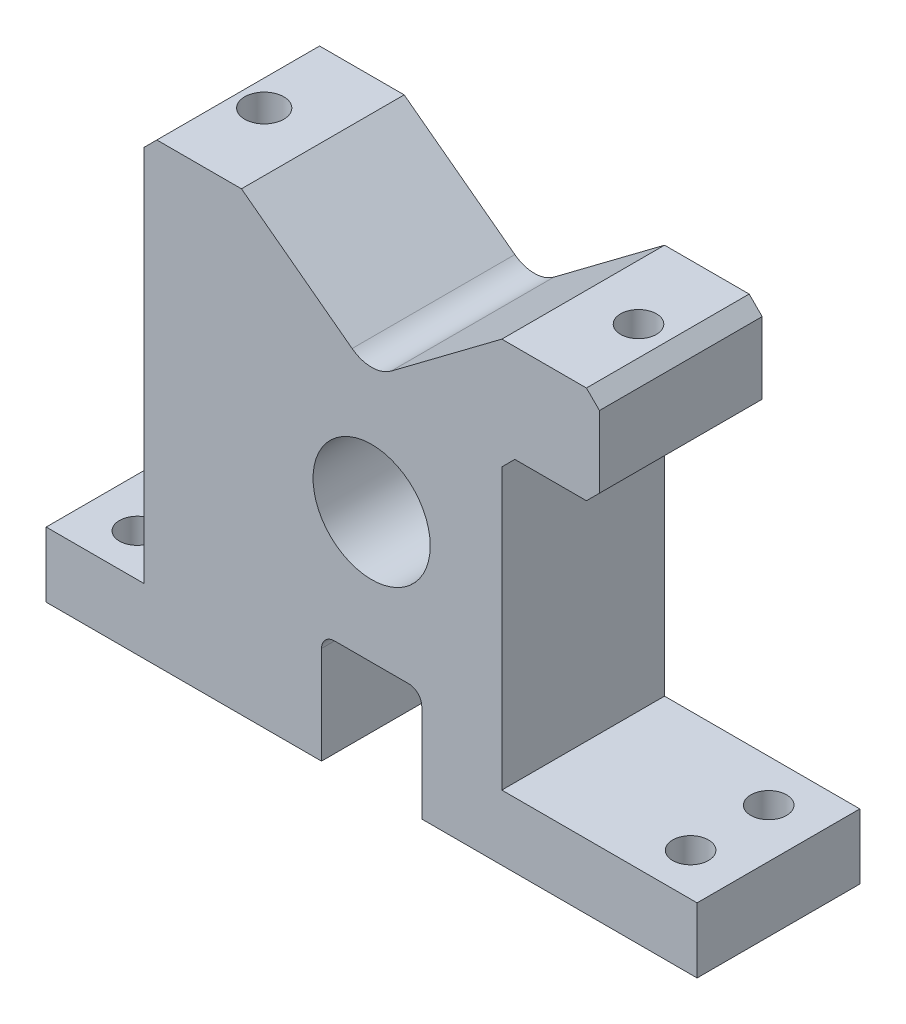
SolidWorks part; units mm, degrees
ref_plane "Front Plane" through (0, 0, 0) normal (0, 0, 1) x (1, 0, 0)
ref_plane "Top Plane" through (0, 0, 0) normal (0, 1, 0) x (1, 0, 0)
ref_plane "Right Plane" through (0, 0, 0) normal (1, 0, 0) x (0, 0, -1)
sketch "Sketch1" plane through (0, 0, 0) normal (0, 0, 1) x (1, 0, 0)
  line L1 (50, 0) -> (50, 10)
  line L2 (50, 10) -> (35, 10)
  line L4 (35, 70) -> (20, 70)
  line L5 (0, 0) -> (0, 37) construction
  line L8 (3, 57.25) -> (20, 70)
  line L9 (-3, 57.25) -> (-20, 70)
  line L10 (-35, 70) -> (-20, 70)
  line L11 (-35, 10) -> (-35, 70)
  line L12 (-50, 10) -> (-35, 10)
  line L13 (-50, 0) -> (-50, 10)
  line L14 (35, 70) -> (35, 55)
  line L16 (-5.7, 17) -> (5.7, 17)
  line L17 (7.7, 15) -> (7.7, 0)
  line L18 (7.7, 0) -> (50, 0)
  line L19 (-7.7, 0) -> (-50, 0)
  line L20 (35, 55) -> (20, 55)
  line L21 (20, 55) -> (20, 10)
  line L22 (20, 10) -> (35, 10)
  line L23 (-7.7, 15) -> (-7.7, 0)
  arc A1 (3, 57.25) -> (-3, 57.25) centre (0, 61.25) cw
  arc A2 (-7.7, 15) -> (-5.7, 17) centre (-5.7, 15) cw
  arc A3 (7.7, 15) -> (5.7, 17) centre (5.7, 15) ccw
  point P17 (0, 55)
  dimension "D1" = 5
  dimension "D2" = 2
  dimension "D3" = 15.4
extrude "Boss-Extrude1" add sketch "Sketch1" along normal blind 25
sketch "Sketch2" plane through (0, 0, 0) normal (0, 0, -1) x (-1, 0, 0)
  circle A0 centre (0, 37) radius 11.2
extrude "Cut-Extrude1" cut sketch "Sketch2" against normal through all
sketch "Sketch4" plane through (0, 10, 0) normal (0, 1, 0) x (1, 0, 0)
  line L0 (-42.5, 0) -> (-42.5, -6.5) construction
  line L3 (-35, 0) -> (-50, 0) construction
  line L4 (-42.5, -25) -> (-42.5, -18.5) construction
  line L5 (-35, -25) -> (-50, -25) construction
  line L6 (42.5, 0) -> (42.5, -6.5) construction
  line L7 (50, 0) -> (35, 0) construction
  line L8 (42.5, -25) -> (42.5, -18.5) construction
sketch "Sketch9" plane through (0, 70, 0) normal (0, 1, 0) x (1, 0, 0)
  line L0 (27.5, -25) -> (27.5, -12.5) construction
  line L1 (35, -25) -> (20, -25) construction
chamfer "Chamfer2" distance 2 angle 45 4 edges at (20, 55, 12.5) (35, 55, 12.5) (35, 70, 12.5) (-35, 70, 12.5)
sketch "Sketch11" plane through (0, 0, 25) normal (0, 0, 1) x (1, 0, 0)
  circle A0 centre (0, 37) radius 11.4
  circle A1 centre (0, 37) radius 9
extrude "Boss-Extrude3" add sketch "Sketch11" against normal blind 18
hole_wizard "M5 Clearance Hole1" positions "Sketch12" profile "Sketch13" hole size "M5" standard "ISO" end condition up to next
sketch "Sketch12" plane through (0, 10, 0) normal (0, 1, 0) x (1, 0, 0)
  point P0 (42.5, -18.5)
  point P3 (42.5, -6.5)
  point P6 (-42.5, -18.5)
  point P9 (-42.5, -6.5)
sketch "Sketch13" plane through (42.5, 10, 18.5) normal (1, 0, 0) x (0, 0, 1)
  line L0 (0, 0) -> (0, 10)
  line L1 (0, 10) -> (2.75, 10)
  line L2 (2.75, 10) -> (2.75, 0)
  line L5 (2.75, 0) -> (0, 0)
  line L11 (0, -6.35) -> (0, 107.95) construction
  dimension "Thru Hole Dia." = 5.5
  dimension "Thru Hole Depth" = 10
sketch "Sketch16" plane through (0, 70, 0) normal (0, 1, 0) x (1, 0, 0)
  line L0 (33, -12.5) -> (28.5, -12.5) construction
  line L1 (33, -25) -> (33, 0) construction
hole_wizard "M5 Clearance Hole2" positions "Sketch17" profile "Sketch18" hole size "M5" standard "ISO" end condition up to next
sketch "Sketch17" plane through (0, 70, 0) normal (0, 1, 0) x (1, 0, 0)
  point P0 (28.5, -12.5)
sketch "Sketch18" plane through (28.5, 70, 12.5) normal (1, 0, 0) x (0, 0, 1)
  line L0 (0, 0) -> (0, 15)
  line L1 (0, 15) -> (2.75, 15)
  line L2 (2.75, 15) -> (2.75, 0)
  line L5 (2.75, 0) -> (0, 0)
  line L11 (0, -6.35) -> (0, 107.95) construction
  dimension "Thru Hole Dia." = 5.5
  dimension "Thru Hole Depth" = 15
sketch "Sketch19" plane through (0, 70, 0) normal (0, 1, 0) x (1, 0, 0)
  line L0 (-33, -25) -> (-33, -12.5) construction
  line L1 (-33, 0) -> (-33, -25) construction
  line L2 (-33, -12.5) -> (-29, -12.5) construction
hole_wizard "Ø6.0mm Dowel Hole1" positions "Sketch20" profile "Sketch21" hole size "Ø6.0" standard "ISO"
sketch "Sketch20" plane through (0, 70, 0) normal (0, 1, 0) x (1, 0, 0)
  point P0 (-29, -12.5)
sketch "Sketch21" plane through (-29, 70, 12.5) normal (1, 0, 0) x (0, 0, 1)
  line L0 (0, 0) -> (0, 41.8026)
  line L1 (0, 41.8026) -> (3, 40)
  line L2 (3, 40) -> (3, 0)
  line L5 (3, 0) -> (0, 0)
  line L10 (0, 41.8026) -> (-3, 40) construction
  line L11 (0, -6.35) -> (0, 107.95) construction
  dimension "Hole Dia." = 6
  dimension "Hole Depth" = 40
  dimension "Drill Angle" = 118
